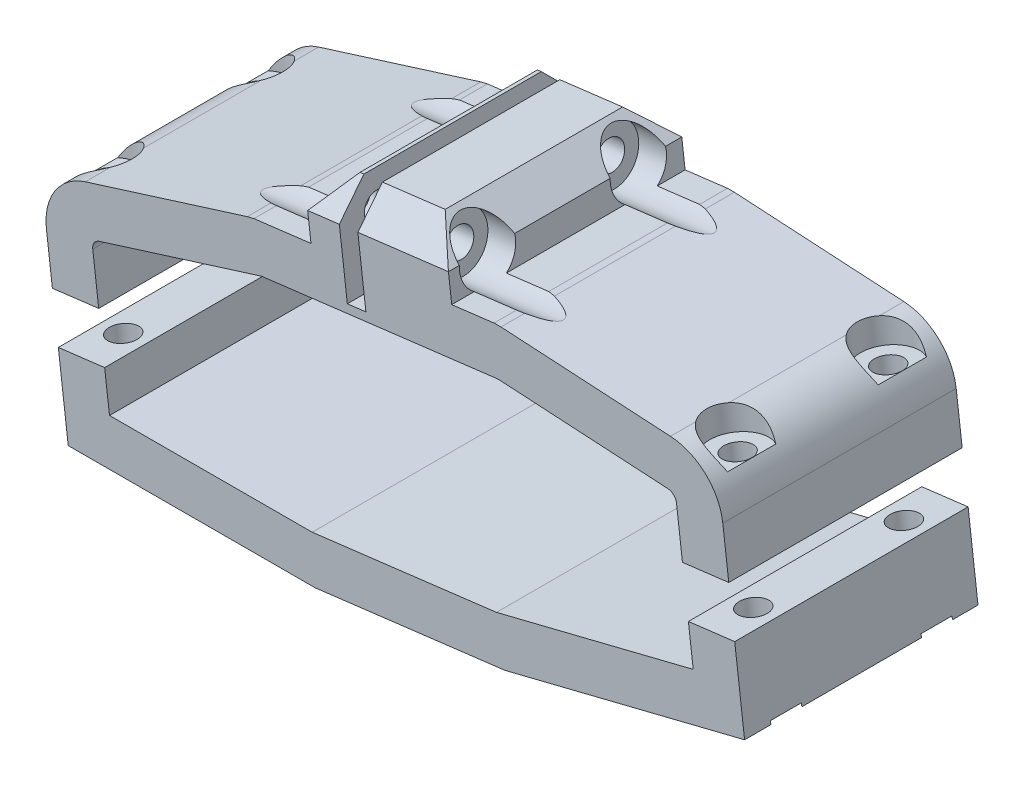
SolidWorks part; units mm, degrees
ref_plane "前视基准面" through (0, 0, 0) normal (0, 0, 1) x (1, 0, 0)
ref_plane "上视基准面" through (0, 0, 0) normal (0, 1, 0) x (1, 0, 0)
ref_plane "右视基准面" through (0, 0, 0) normal (1, 0, 0) x (0, 0, -1)
sketch "Sketch1" plane through (0, 0, 0) normal (0, 0, 1) x (1, 0, 0)
  line L0 (-7.1352, -176.1349) -> (-5.9065, -186.0979)
  line L1 (-5.9065, -186.0979) -> (20.545, -186.0621)
  line L2 (20.545, -186.0621) -> (21.8638, -185.8994)
  line L3 (21.8638, -185.8994) -> (39.5581, -183.7172)
  line L4 (39.5581, -183.7172) -> (40.8769, -183.5546)
  line L5 (40.8769, -183.5546) -> (66.5446, -177.1627)
  line L6 (66.5446, -177.1627) -> (65.3159, -167.1998)
  line L7 (64.2102, -158.2344) -> (65.3159, -167.1998)
  line L8 (58.6068, -152.9791) -> (57.6996, -152.9258)
  line L9 (40.4483, -151.9135) -> (57.6996, -152.9258)
  line L10 (39.7063, -151.9195) -> (40.4483, -151.9135)
  line L11 (13.9945, -155.0904) -> (39.7063, -151.9195)
  line L12 (13.9945, -155.0904) -> (13.2733, -155.2649)
  line L13 (-3.2152, -160.4383) -> (13.2733, -155.2649)
  line L14 (-3.2152, -160.4383) -> (-4.0822, -160.7103)
  line L15 (-7.1352, -176.1349) -> (-8.2409, -167.1695)
  line L126 (-2.1728, -175.5229) -> (-1.486, -181.0919)
  line L127 (20.2344, -181.0625) -> (21.2518, -180.937)
  line L128 (-1.7184, -165.209) -> (14.6111, -160.0855)
  line L129 (-1.7184, -165.209) -> (-2.5854, -165.481)
  line L131 (-2.1728, -175.5229) -> (-3.2785, -166.5575)
  line L132 (14.8914, -160.0177) -> (14.6111, -160.0855)
  line L133 (38.9461, -178.7548) -> (39.9635, -178.6294)
  line L134 (39.9635, -178.6294) -> (61.0403, -173.3807)
  line L135 (21.2518, -180.937) -> (38.9461, -178.7548)
  line L136 (-1.486, -181.0919) -> (20.2344, -181.0625)
  line L198 (14.8914, -160.0177) -> (40.0334, -156.917)
  line L201 (40.0334, -156.917) -> (40.3218, -156.9147)
  line L225 (61.0403, -173.3807) -> (60.3535, -167.8118)
  line L228 (59.2478, -158.8464) -> (60.3535, -167.8118)
  line L230 (58.3139, -157.9705) -> (57.4067, -157.9173)
  line L231 (40.3218, -156.9147) -> (57.4067, -157.9173)
  arc A0 (64.2102, -158.2344) -> (58.6068, -152.9791) centre (58.2553, -158.9688) ccw
  arc A1 (-4.0822, -160.7103) -> (-8.2409, -167.1695) centre (-2.286, -166.4351) ccw
  arc A2 (-2.5854, -165.481) -> (-3.2785, -166.5575) centre (-2.286, -166.4351) ccw
  arc A3 (59.2478, -158.8464) -> (58.3139, -157.9705) centre (58.2553, -158.9688) ccw
  dimension "D1" = 5
extrude "Boss-Extrude1" add sketch "Sketch1" against normal blind 25 from offset 30 offset against normal yes
sketch "Sketch3" plane through (0, 0, -30) normal (0, 0, 1) x (1, 0, 0)
  line L4 (64.8491, -163.4152) -> (65.4863, -168.5817)
  line L5 (64.8491, -163.4152) -> (-10.8514, -172.7511)
  line L6 (65.4863, -168.5817) -> (-10.2142, -177.9176)
  line L7 (-10.8514, -172.7511) -> (-10.2142, -177.9176)
extrude "Cut-Extrude1" cut sketch "Sketch3" against normal through all
sketch "Sketch4" plane through (20.8231, -168.8448, 0) normal (0.1224, -0.9925, 0) x (0.9925, 0.1224, 0)
  line L0 (-26.1404, -55) -> (-26.1404, -30) construction
  line L1 (-23.6404, -55) -> (-28.6404, -55) construction
  line L2 (-23.6404, -30) -> (-28.6404, -30) construction
  line L3 (41.8596, -30) -> (41.8596, -55.9127) construction
  line L4 (44.3596, -30) -> (39.3596, -30) construction
  circle A0 centre (-26.1404, -50.6014) radius 1.5
  circle A1 centre (-26.1404, -34.4691) radius 1.5
  circle A2 centre (41.8596, -34.4691) radius 1.5
  circle A3 centre (41.8596, -50.6014) radius 1.5
extrude "Cut-Extrude2" cut sketch "Sketch4" against normal through all both and the other way through all
sketch "Sketch5" plane through (0, 0, -55) normal (0, 0, -1) x (-1, 0, 0)
  line L0 (-35.1724, -152.4786) -> (-20.0972, -154.3378)
  line L1 (-35.1724, -152.4786) -> (-34.4503, -146.6239)
  line L2 (-20.0972, -154.3378) -> (-19.3752, -148.4831)
  line L4 (-39.7063, -151.9195) -> (-13.9945, -155.0904) construction
  line L6 (-34.4503, -146.6239) -> (-19.3752, -148.4831)
extrude "Boss-Extrude2" add sketch "Sketch5" against normal up to surface (25 mm away) up to face at (27.6856, -160.2771, -30)
chamfer "Chamfer1" distance 3 angle 45 4 edges at (19.3752, -148.4831, -42.5) (26.9128, -147.5535, -30) (34.4503, -146.6239, -42.5) (26.9128, -147.5535, -55)
ref_plane "Plane1" through (22.768, -148.0647, -37.9949) normal (0.9925, 0.1224, 0) x (0, 0, -1)
sketch "Sketch8" plane through (0, 0, -55) normal (0, 0, -1) x (-1, 0, 0)
  line L6 (-24.753, -147.8199) -> (-25.1202, -150.7973)
  line L7 (-23.1352, -151.0421) -> (-22.768, -148.0647)
  line L8 (-22.768, -148.0647) -> (-24.753, -147.8199)
  line L9 (-25.1202, -150.7973) -> (-25.9771, -157.7457)
  line L10 (-25.9771, -157.7457) -> (-23.9921, -157.9905)
  line L11 (-23.9921, -157.9905) -> (-23.1352, -151.0421)
extrude "Cut-Extrude3" cut sketch "Sketch8" against normal through all
sketch "Sketch9" plane through (16.1225, 1.9883, 0) normal (0.9925, 0.1224, 0) x (0, 0, -1)
  circle A0 centre (34.1308, -153.1817) radius 1.5
  circle A1 centre (50.2915, -153.1817) radius 1.5
extrude "Cut-Extrude4" cut sketch "Sketch9" against normal blind 23
sketch "Sketch10" plane through (16.1225, 1.9883, 0) normal (0.9925, 0.1224, 0) x (0, 0, -1)
  circle A0 centre (34.1308, -153.1817) radius 3
  circle A1 centre (50.2915, -153.1817) radius 3
extrude "Cut-Extrude5" cut sketch "Sketch10" against normal blind 3 and the other way blind 13
sketch "Sketch11" plane through (1.0474, 0.1292, 0) normal (-0.9925, -0.1224, 0) x (0, 0, 1)
  circle A4 centre (-34.1308, -153.1817) radius 3
  circle A6 centre (-50.2915, -153.1817) radius 3
extrude "Cut-Extrude6" cut sketch "Sketch11" against normal blind 1 and the other way blind 10
sketch "Sketch12" plane through (20.8231, -168.8448, 0) normal (0.1224, -0.9925, 0) x (0.9925, 0.1224, 0)
  circle A0 centre (-26.1404, -50.6014) radius 3
  circle A1 centre (-26.1404, -34.4691) radius 3
extrude "Cut-Extrude7" cut sketch "Sketch12" against normal blind 10.5 from offset 24
extrude "Cut-Extrude8" cut sketch "Sketch12<2>" along normal blind 11.5 from offset 20 offset against normal yes
sketch "Sketch12<2>" plane through (20.8231, -168.8448, 0) normal (0.1224, -0.9925, 0) x (0.9925, 0.1224, 0) same geometry as "Sketch12"
ref_plane "Plane2" through (7.8005, 0.962, 0) normal (0.9925, 0.1224, 0) x (0, 0, -1)
mirror "Mirror1" about plane through (7.8005, 0.962, 0) normal (0.9925, 0.1224, 0) of "Cut-Extrude7"
mirror "Mirror2" about plane through (7.8005, 0.962, 0) normal (0.9925, 0.1224, 0) of "Cut-Extrude8"
